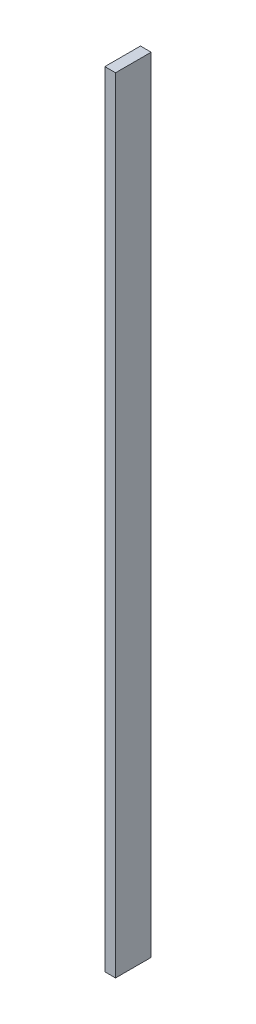
SolidWorks part; units mm, degrees
material "1023 Kohlenstoffstahlblech (SS)"
ref_plane "Ebene vorne" through (0, 0, 0) normal (0, 0, 1) x (1, 0, 0)
ref_plane "Ebene oben" through (0, 0, 0) normal (0, 1, 0) x (1, 0, 0)
ref_plane "Ebene rechts" through (0, 0, 0) normal (1, 0, 0) x (0, 0, -1)
sketch "Skizze1" plane through (0, 0, 0) normal (0, 1, 0) x (1, 0, 0)
  line L1 (-1.5, -5) -> (1.5, -5)
  line L2 (-1.5, -5) -> (-1.5, 5)
  line L3 (-1.5, 5) -> (1.5, 5)
  line L4 (1.5, -5) -> (1.5, 5)
  line L5 (-1.5, -5) -> (1.5, 5) construction
  line L6 (-1.5, 5) -> (1.5, -5) construction
  line L7 (-4, -13.3333) -> (4, -13.3333) construction
  line L8 (-4, -13.3333) -> (-4, 13.3333) construction
  line L9 (-4, 13.3333) -> (4, 13.3333) construction
  line L10 (4, -13.3333) -> (4, 13.3333) construction
  line L11 (-4, -13.3333) -> (4, 13.3333) construction
  line L12 (-4, 13.3333) -> (4, -13.3333) construction
  point P0 (0, 0)
  point P5 (0, 0)
  dimension "D1" = 10
  dimension "D2" = 8
  dimension "D3" = 3
extrude "Aufsatz-Linear austragen1" add sketch "Skizze1" along normal blind 219.8
